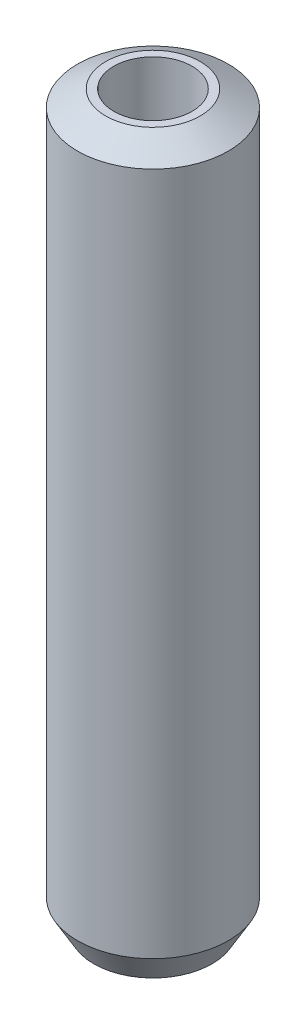
SolidWorks part; units mm, degrees
ref_plane "Front Plane" through (0, 0, 0) normal (0, 0, 1) x (1, 0, 0)
ref_plane "Top Plane" through (0, 0, 0) normal (0, 1, 0) x (1, 0, 0)
ref_plane "Right Plane" through (0, 0, 0) normal (1, 0, 0) x (0, 0, -1)
sketch "Sketch1" plane through (0, 0, 0) normal (0, 1, 0) x (1, 0, 0)
  circle A0 centre (0, 0) radius 17.5
  dimension "SHAFT_OD" = 35
extrude "Boss-Extrude1" add sketch "Sketch1" along normal blind 168.9906
sketch "Sketch2" plane through (0, 0, 0) normal (0, 1, 0) x (1, 0, 0)
  circle A0 centre (0, 0) radius 9.082
  dimension "BORE_D" = 18.1639
extrude "Cut-Extrude1" cut sketch "Sketch2" along normal through all
chamfer "Chamfer1" distance 3.7773 angle 60 2 edges at (0, 168.9906, 17.5) (0, 0, 17.5) first distance on face at (0, 168.9906, 17.5) first distance on face at (0, 0, 9.082)
